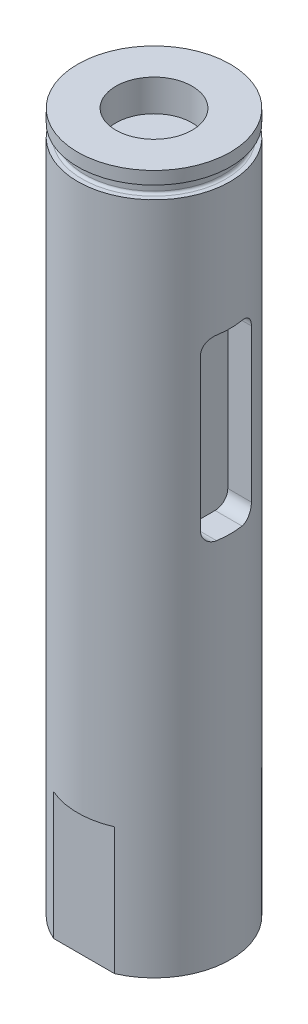
SolidWorks part; units mm, degrees
note: '?' marks a value the reader was unsure of.
ref_plane "前视基准面" through (0, 0, 0) normal (0, 0, 1) x (1, 0, 0)
ref_plane "上视基准面" through (0, 0, 0) normal (0, 1, 0) x (1, 0, 0)
ref_plane "右视基准面" through (0, 0, 0) normal (1, 0, 0) x (0, 0, -1)
sketch "Sketch1" plane through (0, 0, 0) normal (0, 1, 0) x (1, 0, 0)
  line L1 (-8.4121, 0) -> (-6, 0) construction
  line L4 (3.8, -2) -> (3.8, -4.1759) construction
  line L7 (6, 3.6442) -> (6, 2) construction
  line L8 (3.8, 4.5328) -> (3.8, 2) construction
  line L12 (3.8, 0) -> (5, 0) construction
  arc A0 (5.6569, 2) -> (5.6569, -2) centre (0, 0) ccw
  arc A1 (5.6569, 2) -> (5.6569, -2) centre (0, 0) ccw construction
  arc A2 (5.6569, -2) -> (5.6569, 2) centre (0, 0) ccw
  point P8 (7.8, 0)
  dimension "D3" = 6
extrude "Boss-Extrude1" add sketch "Sketch1" along normal blind 14
sketch "Sketch2" plane through (0, 14, 0) normal (0, 1, 0) x (1, 0, 0)
  circle A0 centre (0, 0) radius 6
  dimension "D1" = 12
extrude "Boss-Extrude2" add sketch "Sketch2" along normal blind 12
sketch "Sketch3" plane through (0, 0, 0) normal (0, -1, 0) x (1, 0, 0)
  circle A0 centre (0, 0) radius 6
  dimension "D1" = 12
extrude "Boss-Extrude3" add sketch "Sketch3" along normal blind 15
ref_plane "Plane6" through (0, 24.35, 0) normal (0, 1, 0) x (1, 0, 0)
sketch3d "3DSketch1"
  point P0 (5.8439, 5.7238, 1.3597)
ref_axis "Axis1" through (0, 26, 0) along (0, -1, 0)?
ref_plane "Plane5" through (0, 0, 0) normal (-0.2266, 0, 0.974) x (-0.2751, -0.9593, -0.064)
sketch "Groove Sketch" plane through (1.6043, 12.1829, 0.3733) normal (-0.2266, 0, 0.974) x (-0.9343, 0.2824, -0.2174)
  line L0 (10.6201, -10.2342) -> (12.0831, -9.8034)
  line L1 (12.0831, -9.8034) -> (11.8006, -8.8442)
  line L2 (11.8006, -8.8442) -> (10.3377, -9.2749)
  line L3 (10.2023, -9.5232) -> (10.3718, -10.0988)
  line L4 (15.1493, -45.6204) -> (-11.9454, 46.402) construction
  line L5 (-0.273, -14.484) -> (11.2383, -11.0946) construction
  line L6 (5.4826, -12.7893) -> (-6.0977, 26.5413) construction
  arc A0 (10.3718, -10.0988) -> (10.6201, -10.2342) centre (10.5637, -10.0423) ccw
  arc A1 (10.2023, -9.5232) -> (10.3377, -9.2749) centre (10.3942, -9.4668) cw
  point P10 (10.2871, -9.811)
  dimension "Radius" = 0.2
  dimension "ID" = 10.9
  dimension "OD" = 14.35
  dimension "Width" = 1
  dimension "Location" = 1.5
revolve "Retaining Ring Groove" cut sketch "Groove Sketch" angle 360 about L4 reverse direction yes
other "c-ring<1>"
ref_plane "Plane7" through (6, 0, 0) normal (1, 0, 0) x (0, 0, -1)
sketch "Sketch21" plane through (6, 0, 0) normal (1, 0, 0) x (0, 0, -1)
  line L0 (0, 15.3152) -> (0, -9.2711) construction
  line L1 (-10.3418, 7) -> (16.8832, 7) construction
  line L3 (-1, 14) -> (1, 14)
  line L4 (-2, 13) -> (-2, 1)
  line L5 (-1, 0) -> (1, 0)
  line L6 (2, 13) -> (2, 1)
  line L7 (-2, 14) -> (2, 0) construction
  line L8 (-2, 0) -> (2, 14) construction
  arc A0 (1, 0) -> (2, 1) centre (1, 1) ccw
  arc A1 (-2, 1) -> (-1, 0) centre (-1, 1) ccw
  arc A2 (1, 14) -> (2, 13) centre (1, 13) cw
  arc A3 (-1, 14) -> (-2, 13) centre (-1, 13) ccw
  point P5 (0, 7)
  point P7 (0, 7)
  dimension "D3" = 1
  dimension "D1" = 7
  dimension "D2" = 4
extrude "Cut-Extrude1" cut sketch "Sketch21" against normal blind 2.2
sketch "Sketch22" plane through (0, -15, 0) normal (0, -1, 0) x (1, 0, 0)
  line L0 (-2.4688, -5.5) -> (-2.3979, -5.5) construction
  arc A1 (2.3979, -5.5) -> (-2.3979, -5.5) centre (0, 0) ccw
  arc A2 (2.3979, -5.5) -> (-2.3979, -5.5) centre (0, 0) cw
  dimension "D1" = 5.5
extrude "Boss-Extrude4" add sketch "Sketch22" along normal blind 14
ref_plane "Plane8" through (0, 0, 6) normal (0, 0, 1) x (1, 0, 0)
sketch "Sketch23" plane through (0, -29, 0) normal (0, -1, 0) x (1, 0, 0)
  line L0 (-1.9605, 5.5) -> (2.1478, 5.5) construction
  line L1 (-2.3979, 5.5) -> (2.3979, 5.5)
  circle A0 centre (0, 0) radius 6 construction
  arc A1 (2.3979, 5.5) -> (-2.3979, 5.5) centre (0, 0) ccw
  dimension "D1" = 5.5
extrude "Cut-Extrude2" cut sketch "Sketch23" against normal blind 10
sketch "Sketch24" plane through (0, 26, 0) normal (0, 1, 0) x (1, 0, 0)
  circle A0 centre (0, 0) radius 3
extrude "Cut-Extrude3" cut sketch "Sketch24" against normal blind 2.5
sketch "Sketch25" plane through (0, -29, 0) normal (0, -1, 0) x (1, 0, 0)
  point P0 (0, 0)
hole_wizard "M4 Tapped Hole1" positions "Sketch26" profile "Sketch27" tap size "M4" standard "DIN"
sketch "Sketch26" plane through (0, -29, 0) normal (0, -1, 0) x (-1, 0, 0)
  point P0 (0, 0)
cosmetic thread "Hole Thread1" parameters "D1"=9.2, "D2"=4
sketch "Sketch27" plane through (0, -29, 0) normal (1, 0, 0) x (0, 0, -1)
  line L0 (0, 0) -> (0, 10.9914)
  line L1 (0, 10.9914) -> (1.65, 10)
  line L2 (1.65, 10) -> (1.65, 0)
  line L5 (1.65, 0) -> (0, 0)
  line L10 (0, 10.9914) -> (-1.65, 10) construction
  line L11 (0, -6.35) -> (0, 107.95) construction
  dimension "Tap Drill Dia." = 3.3
  dimension "Tap Drill Depth" = 10
  dimension "Drill Angle" = 118
